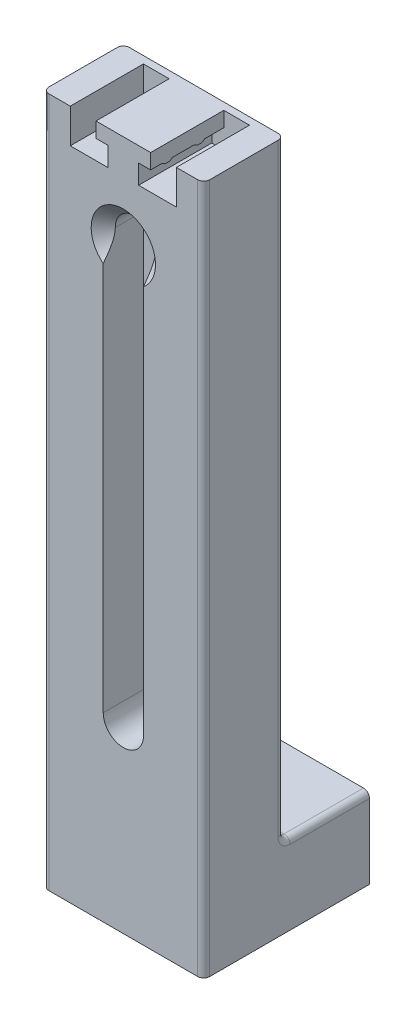
SolidWorks part; units mm, degrees
ref_plane "Front Plane" through (0, 0, 0) normal (0, 0, 1) x (1, 0, 0)
ref_plane "Top Plane" through (0, 0, 0) normal (0, 1, 0) x (1, 0, 0)
ref_plane "Right Plane" through (0, 0, 0) normal (1, 0, 0) x (0, 0, -1)
sketch "Sketch1" plane through (0, 0, 0) normal (0, 1, 0) x (1, 0, 0)
  line L1 (-20, 10) -> (20, 10)
  line L2 (-20, 10) -> (-20, -10)
  line L3 (-20, -10) -> (20, -10)
  line L4 (20, 10) -> (20, -10)
  line L5 (-20, 10) -> (20, -10) construction
  line L6 (-20, -10) -> (20, 10) construction
  point P0 (0, 0)
  dimension "D1" = 40
  dimension "D2" = 20
extrude "Boss-Extrude1" add sketch "Sketch1" along normal blind 171.7
sketch "Sketch2" plane through (0, 0, -10) normal (0, 0, -1) x (-1, 0, 0)
  line L0 (-20, 171.7) -> (-20, 0) construction
  line L1 (-20, 20) -> (20, 20)
  line L2 (-20, 20) -> (-20, 0)
  line L3 (-20, 0) -> (20, 0)
  line L4 (20, 20) -> (20, 0)
  dimension "D1" = 20
extrude "Boss-Extrude2" add sketch "Sketch2" along normal blind 21.25
sketch "Sketch3" plane through (0, 0, 0) normal (0, -1, 0) x (1, 0, 0)
  line L0 (13.2, -31.25) -> (13.2, -22.7)
  line L1 (13.2, -22.7) -> (3.8, -22.7)
  line L2 (3.8, -22.7) -> (3.8, -27.5)
  line L3 (3.8, -27.5) -> (6.8, -27.5)
  line L4 (6.8, -27.5) -> (6.8, -31.25)
  line L5 (6.8, -31.25) -> (13.2, -31.25)
  line L6 (20, 10) -> (20, -31.25) construction
  line L7 (20, -31.25) -> (-20, -31.25) construction
  point P6 (10, -31.25)
  dimension "D1" = 3.75
  dimension "D2" = 9.4
  dimension "D3" = 4.8
  dimension "D4" = 6.4
  dimension "D5" = 10
extrude "Cut-Extrude1" cut sketch "Sketch3" against normal blind 18.2
sketch "Sketch4" plane through (3.8, 0, 0) normal (1, 0, 0) x (0, 0, -1)
  line L0 (27.5, 5.4) -> (27.5, 2.9)
  line L1 (27.5, 5.4) -> (27, 5.4)
  line L2 (27, 5.4) -> (27, 2.9)
  line L3 (27.5, 2.9) -> (27, 2.9)
  line L4 (27.5, 13.4) -> (27.5, 10.9)
  line L5 (27.5, 10.9) -> (27, 10.9)
  line L6 (27.5, 13.4) -> (27, 13.4)
  line L7 (27, 13.4) -> (27, 10.9)
  line L8 (27.5, 18.2) -> (31.25, 18.2) construction
  line L9 (27.5, 0) -> (31.25, 0) construction
  line L10 (27.5, 18.2) -> (27.5, 0) construction
  point P4 (27.5, 12.15)
  point P11 (27.5, 4.15)
  dimension "D1" = 2.5
  dimension "D2" = 0.5
  dimension "D3" = 2.5
  dimension "D4" = 0.5
  dimension "D5" = 6.05
  dimension "D6" = 4.15
extrude "Boss-Extrude3" add sketch "Sketch4" along normal blind 3
fillet "Fillet1" radius 1.5 4 edges at (5.3, 13.4, -27) (5.3, 2.9, -27) (5.3, 5.4, -27) (5.3, 10.9, -27)
sketch "Sketch5" plane through (0, 0, 10) normal (0, 0, 1) x (1, 0, 0)
  line L0 (-13.2, 171.7) -> (-13.2, 163.15)
  line L1 (-13.2, 163.15) -> (-3.8, 163.15)
  line L2 (-3.8, 163.15) -> (-3.8, 167.95)
  line L3 (-3.8, 167.95) -> (-6.8, 167.95)
  line L4 (-6.8, 167.95) -> (-6.8, 171.7)
  line L5 (-6.8, 171.7) -> (-13.2, 171.7)
  line L6 (-20, 171.7) -> (-20, 0) construction
  line L7 (-20, 171.7) -> (20, 171.7) construction
  point P6 (-10, 171.7)
  dimension "D1" = 3.75
  dimension "D2" = 9.4
  dimension "D3" = 4.8
  dimension "D4" = 6.4
  dimension "D5" = 10
extrude "Cut-Extrude2" cut sketch "Sketch5" against normal blind 18.2
sketch "Sketch6" plane through (-3.8, 0, 0) normal (-1, 0, 0) x (0, 0, 1)
  line L0 (4.6, 167.95) -> (7.1, 167.95)
  line L1 (4.6, 167.95) -> (4.6, 167.45)
  line L2 (4.6, 167.45) -> (7.1, 167.45)
  line L3 (7.1, 167.95) -> (7.1, 167.45)
  line L4 (-3.4, 167.95) -> (-0.9, 167.95)
  line L5 (-0.9, 167.95) -> (-0.9, 167.45)
  line L6 (-3.4, 167.95) -> (-3.4, 167.45)
  line L7 (-3.4, 167.45) -> (-0.9, 167.45)
  line L8 (-8.2, 167.95) -> (-8.2, 171.7) construction
  line L9 (10, 167.95) -> (10, 171.7) construction
  line L11 (-8.2, 167.95) -> (10, 167.95) construction
  point P4 (5.85, 167.95)
  point P9 (-2.15, 167.95)
  dimension "D1" = 2.5
  dimension "D2" = 0.5
  dimension "D3" = 2.5
  dimension "D4" = 0.5
  dimension "D5" = 6.05
  dimension "D6" = 4.15
extrude "Boss-Extrude4" add sketch "Sketch6" along normal blind 3
fillet "Fillet2" radius 1.5 4 edges at (-5.3, 167.45, 7.1) (-5.3, 167.45, 4.6) (-5.3, 167.45, -0.9) (-5.3, 167.45, -3.4)
mirror "Mirror1" about plane through (0, 0, 0) normal (1, 0, 0) of "Fillet2", "Boss-Extrude4", "Cut-Extrude2", "Boss-Extrude3", "Cut-Extrude1", "Fillet1"
fillet "Fillet3" radius 1.5 7 edges at (0, 20, -10) (-20, 20, -20.625) (20, 20, -20.625) (20, 85.85, 10) (-20, 85.85, 10) (20, 95.85, -10) (-20, 95.85, -10)
sketch "Sketch7" plane through (0, 0, -10) normal (0, 0, -1) x (-1, 0, 0)
  line L0 (-6.8, 0) -> (6.8, 0) construction
  line L1 (-20, 21.5) -> (-20, 171.7) construction
  circle A0 centre (0, 45.1) radius 5
  dimension "D1" = 45.1
  dimension "D2" = 20
extrude "Cut-Extrude3" cut sketch "Sketch7" against normal through all
sketch "Sketch8" plane through (0, 0, 10) normal (0, 0, 1) x (1, 0, 0)
  line L2 (-5, 45.1) -> (-5, 148.15)
  line L4 (5, 45.1) -> (5, 148.15)
  line L5 (-13.2, 163.15) -> (-3.8, 163.15) construction
  circle A0 centre (0, 45.1) radius 5 construction
  arc A1 (5, 148.15) -> (-5, 148.15) centre (0, 148.15) ccw
  arc A2 (-5, 45.1) -> (5, 45.1) centre (0, 45.1) ccw
  point P7 (0, 153.15)
  dimension "D1" = 10
extrude "Cut-Extrude4" cut sketch "Sketch8" against normal blind 10
chamfer "Chamfer2" distance 5 angle 45 1 edges at (0, 50.1, 0)
chamfer "Chamfer3" distance 3 angle 45 1 edges at (0, 153.15, 10) tangent propagation no
